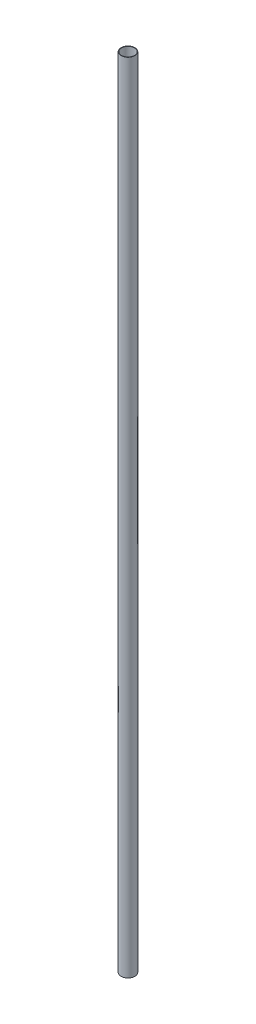
SolidWorks part; units mm, degrees
ref_plane "Front Plane" through (0, 0, 0) normal (0, 0, 1) x (1, 0, 0)
ref_plane "Top Plane" through (0, 0, 0) normal (0, 1, 0) x (1, 0, 0)
ref_plane "Right Plane" through (0, 0, 0) normal (1, 0, 0) x (0, 0, -1)
sketch "Sketch1" plane through (0, 0, 0) normal (0, 1, 0) x (1, 0, 0)
  circle A0 centre (0, 0) radius 20.955
  circle A1 centre (0, 0) radius 19.685
  dimension "D1" = 41.91
  dimension "D2" = 39.37
extrude "Boss-Extrude1" add sketch "Sketch1" along normal blind 2413
